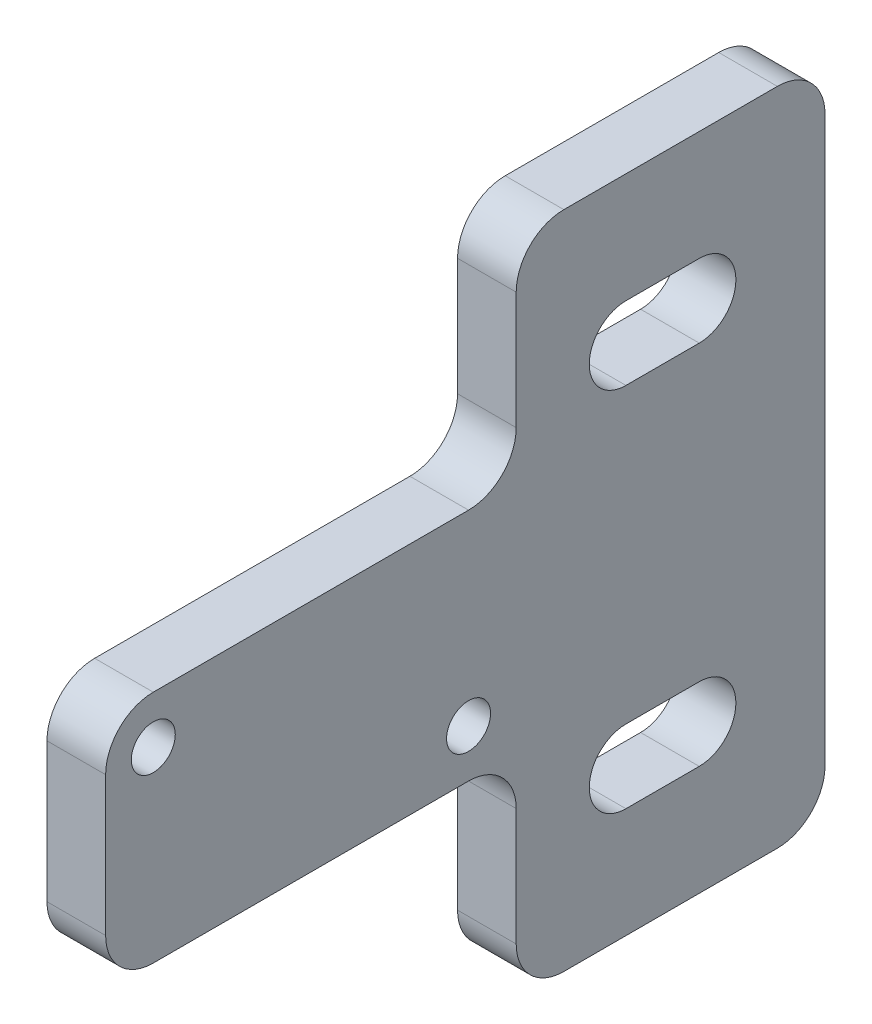
SolidWorks part; units mm, degrees
ref_plane "Front Plane" through (0, 0, 0) normal (1, 0, 0) x (0, 1, 0)
ref_plane "Top Plane" through (0, 0, 0) normal (0, 0, 1) x (0, 1, 0)
ref_plane "Right Plane" through (0, 0, 0) normal (0, 1, 0) x (-1, 0, 0)
sketch "Sketch1" plane through (0, 0, 0) normal (1, 0, 0) x (0, 1, 0)
  line L0 (-4.5, -7.4834) -> (-4.5, -12.4834) construction
  line L1 (0, 0) -> (16, 0)
  line L2 (0, 0) -> (0, 28)
  line L3 (0, 28) -> (16, 28)
  line L4 (16, 0) -> (16, 28)
  line L9 (-2, -7.4834) -> (-2, -12.4834)
  line L10 (-7, -7.4834) -> (-7, -12.4834)
  line L11 (20.5, -7.4834) -> (20.5, -12.4834) construction
  line L12 (23, -7.4834) -> (23, -12.4834)
  line L13 (18, -7.4834) -> (18, -12.4834)
  line L14 (0, -9.9834) -> (45, -9.9834) construction
  line L15 (8, -20) -> (8, 0) construction
  line L17 (-14.5, 0) -> (30.5, 0)
  line L18 (-14.5, 0) -> (-14.5, -21.0619)
  line L19 (-14.5, -21.0619) -> (30.5, -21.0619)
  line L20 (30.5, 0) -> (30.5, -21.0619)
  circle A0 centre (12.75, 24.75) radius 1.5
  circle A1 centre (3.25, 3.25) radius 1.5
  arc A2 (-2, -7.4834) -> (-7, -7.4834) centre (-4.5, -7.4834) ccw
  arc A3 (-7, -12.4834) -> (-2, -12.4834) centre (-4.5, -12.4834) ccw
  arc A4 (23, -7.4834) -> (18, -7.4834) centre (20.5, -7.4834) ccw
  arc A5 (18, -12.4834) -> (23, -12.4834) centre (20.5, -12.4834) ccw
  point P14 (-4.5, -9.9834)
  point P19 (20.5, -9.9834)
  point P31 (21.8619, -12.4834)
  dimension "D3" = 3
  dimension "D9" = 10
  dimension "D1" = 16
  dimension "D2" = 28
  dimension "D4" = 3.25
  dimension "D5" = 3.25
  dimension "D6" = 3.25
  dimension "D7" = 3.25
  dimension "D8" = 5
  dimension "D10" = 45
  dimension "D12" = 25
extrude "Boss-Extrude1" add sketch "Sketch1" along normal blind 4 contours L1 L4 L3 L2 A1 A0 | L18 L1 A5 L13 A4 L12 A3 L10 A2 L9 region at (0, 8, 14) region at (0, 8, -10.5879)
fillet "Fillet1" radius 3.25 8 edges at (2, 0, 28) (2, 16, 0) (2, 30.5, 0) (2, 30.5, -21.0619) (2, -14.5, -21.0619) (2, -14.5, 0) (2, 0, 0) (2, 16, 28)
